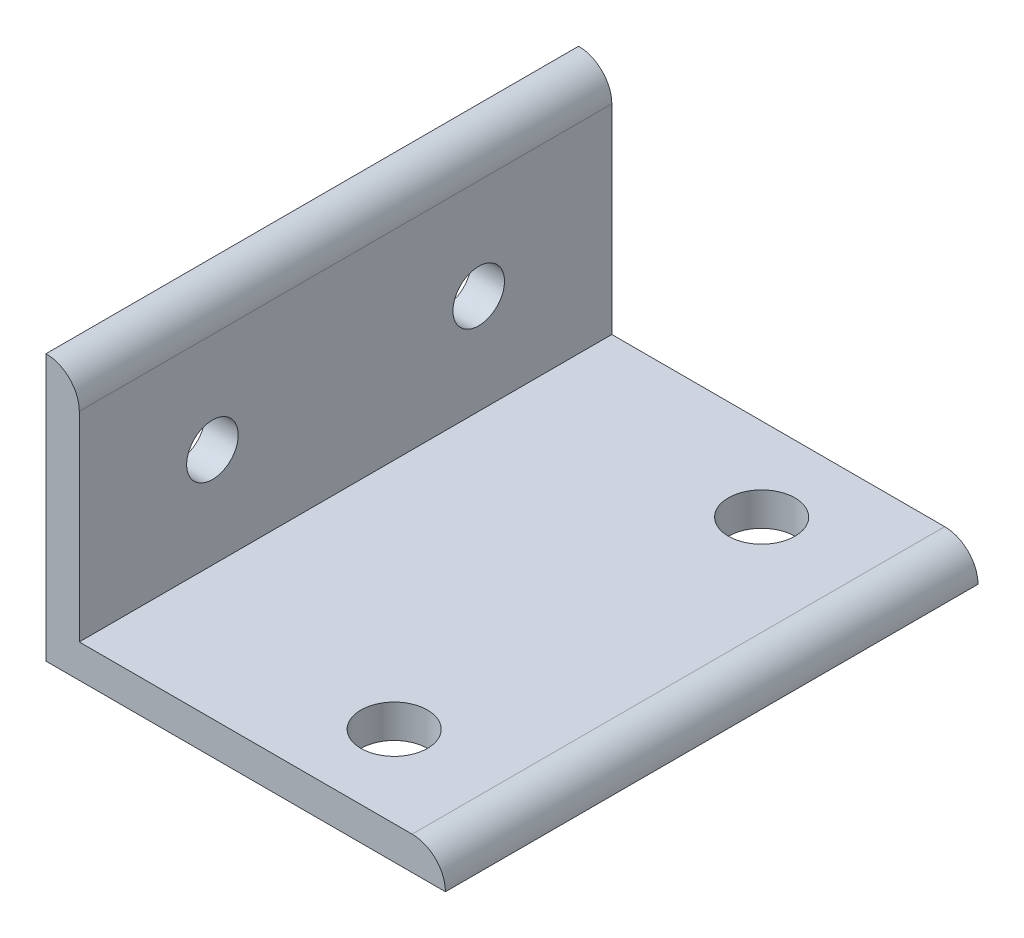
SolidWorks part; units mm, degrees
ref_plane "Front Plane" through (0, 0, 0) normal (0, 0, 1) x (1, 0, 0)
ref_plane "Top Plane" through (0, 0, 0) normal (0, 1, 0) x (1, 0, 0)
ref_plane "Right Plane" through (0, 0, 0) normal (1, 0, 0) x (0, 0, -1)
sketch "Sketch1" plane through (0, 0, 0) normal (0, 0, 1) x (1, 0, 0)
  line L0 (-8.1265, 19.7682) -> (-8.1265, -5.6318)
  line L1 (-8.1265, -5.6318) -> (29.9735, -5.6318)
  line L2 (29.9735, -5.6318) -> (29.9735, -2.4568)
  line L3 (29.9735, -2.4568) -> (-4.9515, -2.4568)
  line L4 (-4.9515, -2.4568) -> (-4.9515, 19.7682)
  line L5 (-4.9515, 19.7682) -> (-8.1265, 19.7682)
  dimension "D1" = 3.175
  dimension "D2" = 3.175
  dimension "D3" = 38.1
  dimension "D4" = 25.4
extrude "Boss-Extrude1" add sketch "Sketch1" along normal mid plane 50.8
hole_wizard "1/4 (0.25) Diameter Hole1" positions "Sketch5" profile "Sketch4" hole size "1/4" standard "ANSI Inch"
sketch "Sketch5" plane through (0, -2.4568, 0) normal (0, 1, 0) x (1, 0, 0)
  line L0 (29.9735, -25.4) -> (29.9735, 25.4) construction
  line L1 (29.9735, 25.4) -> (-4.9515, 25.4) construction
  point P0 (17.2735, 17.4625)
  point P13 (17.2735, -17.5895)
  dimension "D1" = 12.7
  dimension "D2" = 7.9375
  dimension "D3" = 2
sketch "Sketch4" plane through (17.2735, -2.4568, -17.4625) normal (1, 0, 0) x (0, 0, 1)
  line L0 (0, 0) -> (0, 19.4337)
  line L1 (0, 19.4337) -> (3.175, 17.526)
  line L2 (3.175, 17.526) -> (3.175, 0)
  line L5 (3.175, 0) -> (0, 0)
  line L10 (0, 19.4337) -> (-3.175, 17.526) construction
  line L11 (0, -6.35) -> (0, 107.95) construction
  dimension "Hole Dia." = 6.35
  dimension "Hole Depth" = 17.526
  dimension "Drill Angle" = 118
hole_wizard "#10 (0.1935) Diameter Hole1" positions "Sketch7" profile "Sketch6" hole size "#10" standard "ANSI Inch"
sketch "Sketch7" plane through (-4.9515, 0, 0) normal (1, 0, 0) x (0, 0, -1)
  line L0 (25.4, -2.4568) -> (25.4, 19.7682) construction
  line L1 (-25.4, 19.7682) -> (25.4, 19.7682) construction
  point P0 (12.7, 7.0682)
  point P20 (-12.7, 7.0682)
  dimension "D1" = 12.7
  dimension "D2" = 12.7
  dimension "D3" = 2
sketch "Sketch6" plane through (-4.9515, 7.0682, -12.7) normal (0, 1, 0) x (0, 0, -1)
  line L0 (0, 0) -> (0, 19.0026)
  line L1 (0, 19.0026) -> (2.4574, 17.526)
  line L2 (2.4574, 17.526) -> (2.4574, 0)
  line L5 (2.4574, 0) -> (0, 0)
  line L10 (0, 19.0026) -> (-2.4575, 17.526) construction
  line L11 (0, -6.35) -> (0, 107.95) construction
  dimension "Hole Dia." = 4.9149
  dimension "Hole Depth" = 17.526
  dimension "Drill Angle" = 118
fillet "Fillet1" radius 3.175 2 edges at (29.9735, -2.4568, 0) (-4.9515, 19.7682, 0)
